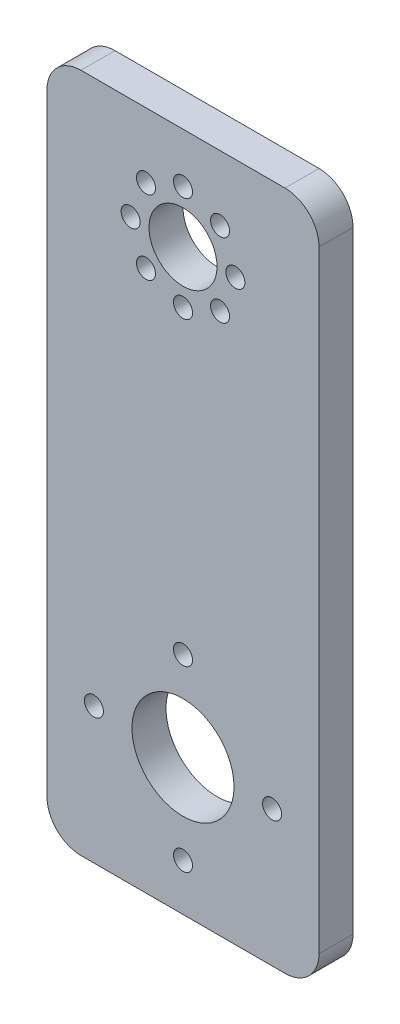
SolidWorks part; units mm, degrees
material "6061-T6 (SS)"
ref_plane "Front Plane" through (0, 0, 0) normal (0, 0, 1) x (1, 0, 0)
ref_plane "Top Plane" through (0, 0, 0) normal (0, 1, 0) x (1, 0, 0)
ref_plane "Right Plane" through (0, 0, 0) normal (1, 0, 0) x (0, 0, -1)
sketch "Sketch1" plane through (0, 0, 0) normal (0, 0, 1) x (1, 0, 0)
  line L1 (0, 0) -> (50.8, 0)
  line L2 (0, 0) -> (0, 127)
  line L3 (0, 127) -> (50.8, 127)
  line L4 (50.8, 0) -> (50.8, 127)
  circle A0 centre (25.4, 25.4) radius 9.525
  circle A5 centre (25.4, 107.95) radius 6.35
  dimension "D1" = 50.8
  dimension "D3" = 19.05
  dimension "D6" = 12.7
  dimension "D2" = 127
  dimension "D4" = 25.4
  dimension "D5" = 101.6
  dimension "D7" = 19.05
  dimension "D8" = 25.4
extrude "Boss-Extrude1" add sketch "Sketch1" along normal blind 6.35
sketch "Sketch2" plane through (0, 0, 6.35) normal (0, 0, 1) x (1, 0, 0)
  line L0 (50.8, 0) -> (50.8, 127) construction
  circle A0 centre (25.4, 42.037) radius 1.778
  circle A1 centre (25.4, 25.4) radius 9.525 construction
  dimension "D1" = 16.637
  dimension "D2" = 3.556
  dimension "D3" = 25.4
extrude "Cut-Extrude1" cut sketch "Sketch2" against normal blind 6.35
pattern_circular "CirPattern1" count 4 over 360 about axis through (25.4, 25.4, 6.35) along (0, 0, 1) of "Cut-Extrude1"
sketch "Sketch3" plane through (0, 0, 6.35) normal (0, 0, 1) x (1, 0, 0)
  line L1 (50.8, 0) -> (50.8, 127) construction
  circle A0 centre (25.4, 117.729) radius 1.778
  circle A1 centre (25.4, 107.95) radius 6.35 construction
  dimension "D1" = 3.556
  dimension "D2" = 25.4
  dimension "D3" = 9.779
extrude "Cut-Extrude2" cut sketch "Sketch3" against normal blind 6.35
pattern_circular "CirPattern2" count 8 over 360 about axis through (25.4, 107.95, 6.35) along (0, 0, 1) of "Cut-Extrude2"
fillet "Fillet1" radius 6.35 4 edges at (0, 0, 3.175) (50.8, 0, 3.175) (0, 127, 3.175) (50.8, 127, 3.175)
